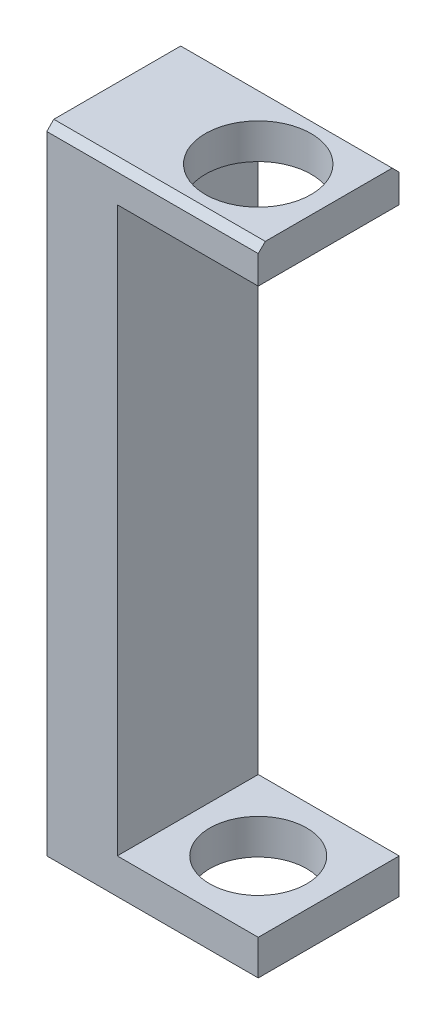
SolidWorks part; units mm, degrees
ref_plane "Front Plane" through (0, 0, 0) normal (0, 0, 1) x (1, 0, 0)
ref_plane "Top Plane" through (0, 0, 0) normal (0, 1, 0) x (1, 0, 0)
ref_plane "Right Plane" through (0, 0, 0) normal (1, 0, 0) x (0, 0, -1)
sketch "Sketch1" plane through (0, 0, 0) normal (0, 1, 0) x (1, 0, 0)
  line L1 (0, 0) -> (76.2, 0)
  line L2 (0, 0) -> (0, 50.8)
  line L3 (0, 50.8) -> (76.2, 50.8)
  line L4 (76.2, 0) -> (76.2, 50.8)
  dimension "D1" = 50.8
  dimension "D2" = 76.2
extrude "Boss-Extrude1" add sketch "Sketch1" along normal blind 228.6
sketch "Sketch2" plane through (0, 0, 0) normal (0, 0, 1) x (1, 0, 0)
  line L0 (76.2, 228.6) -> (76.2, 0) construction
  line L1 (76.2, 215.9) -> (25.4, 215.9)
  line L2 (76.2, 215.9) -> (76.2, 12.7)
  line L3 (76.2, 12.7) -> (25.4, 12.7)
  line L4 (25.4, 215.9) -> (25.4, 12.7)
  line L5 (0, 228.6) -> (76.2, 228.6) construction
  line L6 (0, 0) -> (76.2, 0) construction
  dimension "D1" = 12.7
  dimension "D2" = 12.7
  dimension "D3" = 50.8
extrude "Cut-Extrude1" cut sketch "Sketch2" against normal through all
sketch "Sketch5" plane through (0, 228.6, 0) normal (0, 1, 0) x (1, 0, 0)
  line L0 (25.4, 50.8) -> (25.4, 0) construction
  line L1 (25.4, 50.8) -> (25.4, 0) construction
  line L2 (25.4, 50.8) -> (76.2, 0) construction
  circle A0 centre (50.8, 25.4) radius 19.05
  dimension "D1" = 38.1
extrude "Cut-Extrude2" cut sketch "Sketch5" against normal up to next
sketch "Sketch8" plane through (0, 0, 0) normal (0, -1, 0) x (1, 0, 0)
  line L0 (25.4, -50.8) -> (25.4, 0) construction
  line L1 (25.4, -50.8) -> (25.4, 0) construction
  line L2 (25.4, 0) -> (76.2, -50.8) construction
  circle A0 centre (50.8, -25.4) radius 17.4625
  dimension "D1" = 34.925
extrude "Cut-Extrude3" cut sketch "Sketch8" against normal up to next
hole_wizard "#10-32 Tapped Hole1" positions "Sketch10" profile "Sketch9" tap size "#10-32" standard "ANSI Inch"
sketch "Sketch10" plane through (0, 0, 0) normal (0, -1, 0) x (-1, 0, 0)
  line L0 (-25.4, 50.8) -> (-25.4, 0) construction
  line L1 (-25.4, 50.8) -> (-25.4, 0) construction
  line L3 (-12.7, 50.8) -> (-12.7, 0) construction
  line L4 (-76.2, 50.8) -> (0, 50.8) construction
  line L5 (0, 0) -> (-76.2, 0) construction
  line L7 (-25.4, 25.4) -> (0, 25.4) construction
  line L8 (0, 50.8) -> (0, 0) construction
  point P0 (-6.35, 44.45)
  point P28 (-12.7, 25.4)
  point P33 (-19.05, 44.45)
  point P35 (-6.35, 6.35)
  point P36 (-19.05, 6.35)
  dimension "D1" = 6.35
  dimension "D2" = 6.35
cosmetic thread "Hole Thread1" parameters "D1"=38.1, "D2"=4.826
cosmetic thread "Hole Thread2" parameters "D1"=38.1, "D2"=4.826
cosmetic thread "Hole Thread3" parameters "D1"=38.1, "D2"=4.826
cosmetic thread "Hole Thread4" parameters "D1"=38.1, "D2"=4.826
sketch "Sketch9" plane through (6.35, 0, -44.45) normal (1, 0, 0) x (0, 0, -1)
  line L0 (0, 0) -> (0, 43.2757)
  line L1 (0, 43.2757) -> (2.0193, 42.0624)
  line L2 (2.0193, 42.0624) -> (2.0193, 0)
  line L5 (2.0193, 0) -> (0, 0)
  line L10 (0, 43.2757) -> (-2.0193, 42.0624) construction
  line L11 (0, -6.35) -> (0, 107.95) construction
  dimension "Tap Drill Dia." = 4.0386
  dimension "Tap Drill Depth" = 42.0624
  dimension "Drill Angle" = 118
chamfer "Chamfer1" distance 2.54 angle 45 2 edges at (38.1, 228.6, -50.8) (38.1, 228.6, 0)
